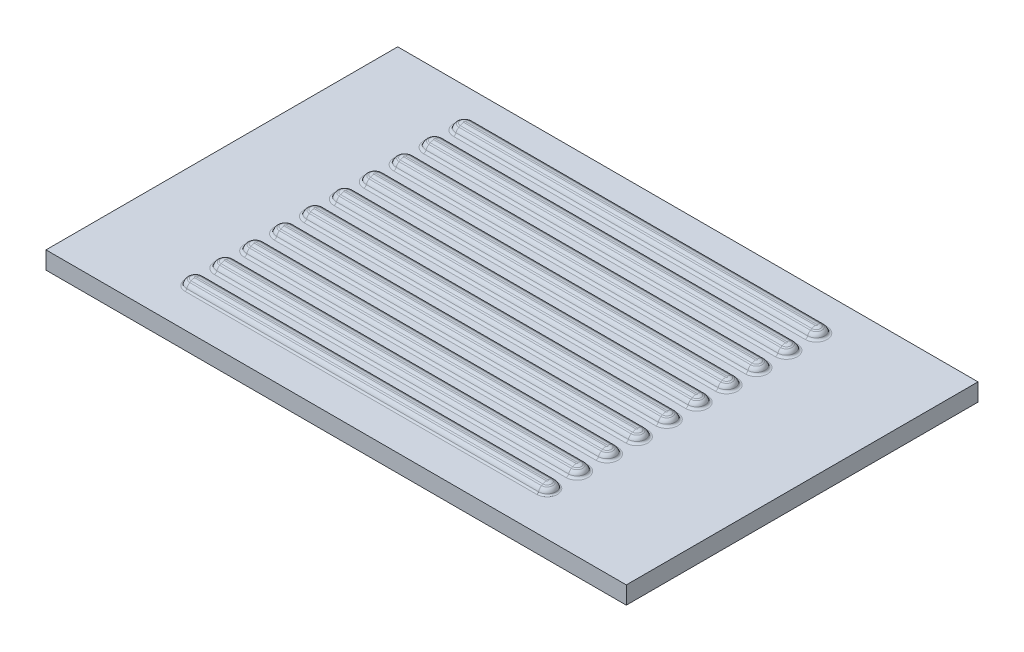
SolidWorks part; units mm, degrees
ref_plane "Front Plane" through (0, 0, 0) normal (0, 0, 1) x (1, 0, 0)
ref_plane "Top Plane" through (0, 0, 0) normal (0, 1, 0) x (1, 0, 0)
ref_plane "Right Plane" through (0, 0, 0) normal (1, 0, 0) x (0, 0, -1)
sketch "Sketch1" plane through (0, 0, 0) normal (0, 1, 0) x (1, 0, 0)
  line L1 (-15000, 10000) -> (15000, 10000)
  line L2 (-15000, 10000) -> (-15000, -10000)
  line L3 (-15000, -10000) -> (15000, -10000)
  line L4 (15000, 10000) -> (15000, -10000)
  line L5 (-15000, 10000) -> (15000, -10000) construction
  line L6 (-15000, -10000) -> (15000, 10000) construction
  point P0 (0, 0)
  dimension "D1" = 20000
  dimension "D2" = 30000
extrude "Boss-Extrude1" add sketch "Sketch1" against normal blind 1000
sketch "Sketch4" plane through (0, 0, 0) normal (0, 1, 0) x (1, 0, 0)
  line L1 (-15000, 10000) -> (-18000, 10000)
  line L2 (-15000, 10000) -> (-15000, -10000)
  line L3 (-15000, -10000) -> (-18000, -10000)
  line L4 (-18000, 10000) -> (-18000, -10000)
  dimension "D1" = 3000
extrude "Boss-Extrude3" add sketch "Sketch4" against normal blind 1000
sketch "Sketch3" plane through (0, 0, 0) normal (0, 1, 0) x (1, 0, 0)
  line L0 (-12000, -7500) -> (8000, -7500) construction
  line L1 (-12000, -7000) -> (8000, -7000)
  line L2 (-12000, -8000) -> (8000, -8000)
  line L3 (-18000, -10000) -> (15000, -10000) construction
  line L6 (-18000, 10000) -> (-18000, -10000) construction
  arc A0 (-12000, -7000) -> (-12000, -8000) centre (-12000, -7500) ccw
  arc A1 (8000, -8000) -> (8000, -7000) centre (8000, -7500) ccw
  point P2 (-2000, -7500)
  dimension "D4" = 6000
  dimension "D1" = 1000
  dimension "D2" = 20000
  dimension "D3" = 2500
extrude "Boss-Extrude2" add sketch "Sketch3" along normal blind 400
chamfer "Chamfer1" distance 200 angle 60 4 edges at (-2000, 400, 7000) (8500, 400, 7500) (-2000, 400, 8000) (-12500, 400, 7500) first distance on face at (-2000, 200, 7000) first distance on face at (8250, 200, 7500) first distance on face at (-2000, 200, 8000) first distance on face at (-12250, 200, 7500)
fillet "Fillet3" radius 400 4 edges at (-2000, 400, 7653.5898) (-12153.5898, 400, 7500) (-2000, 400, 7346.4102) (8153.5898, 400, 7500)
fillet "Fillet4" radius 350 4 edges at (-12500, 200, 7500) (-2000, 200, 8000) (8500, 200, 7500) (-2000, 200, 7000)
fillet "Fillet2" radius 100 4 edges at (8500, 0, 7500) (-2000, 0, 7000) (-12500, 0, 7500) (-2000, 0, 8000)
pattern_linear "LPattern3" count 10 spacing 1700 along (0, 0, -1) of "Boss-Extrude2", "Chamfer1", "Fillet3", "Fillet4"
fillet "Fillet5" radius 150 4 edges at (-2000, 0, 6300) (-12500, 0, 5800) (-2000, 0, 5300) (8500, 0, 5800)
fillet "Fillet6" radius 150 4 edges at (-2000, 0, 4600) (-12500, 0, 4100) (-2000, 0, 3600) (8500, 0, 4100)
fillet "Fillet7" radius 150 4 edges at (-2000, 0, 2900) (-12500, 0, 2400) (-2000, 0, 1900) (8500, 0, 2400)
fillet "Fillet8" radius 150 4 edges at (-2000, 0, 1200) (-12500, 0, 700) (-2000, 0, 200) (8500, 0, 700)
fillet "Fillet9" radius 150 4 edges at (8500, 0, -1000) (-2000, 0, -500) (-12500, 0, -1000) (-2000, 0, -1500)
fillet "Fillet10" radius 150 4 edges at (-2000, 0, -2200) (-12500, 0, -2700) (-2000, 0, -3200) (8500, 0, -2700)
fillet "Fillet11" radius 150 4 edges at (8500, 0, -4400) (-2000, 0, -4900) (-12500, 0, -4400) (-2000, 0, -3900)
fillet "Fillet12" radius 150 4 edges at (8500, 0, -6100) (-2000, 0, -6600) (-12500, 0, -6100) (-2000, 0, -5600)
fillet "Fillet13" radius 150 4 edges at (8500, 0, -7800) (-2000, 0, -8300) (-12500, 0, -7800) (-2000, 0, -7300)
sketch "Sketch5" [suppressed] plane through (0, 0, 0) normal (0, 1, 0) x (1, 0, 0)
  line L0 (-12000, 1000) -> (8000, 1000)
  line L2 (8000, 2946.4102) -> (8000, 2746.4102) construction
  line L3 (8000, 2846.4102) -> (-12000, 2700)
  arc A0 (8000, 1000) -> (8000, 2846.4102) centre (8006.7583, 1923.2051) ccw
  arc A1 (-12000, 2700) -> (-11987.5551, 1000) centre (-11993.7776, 1850) ccw
  dimension "D1" = 850.0228
